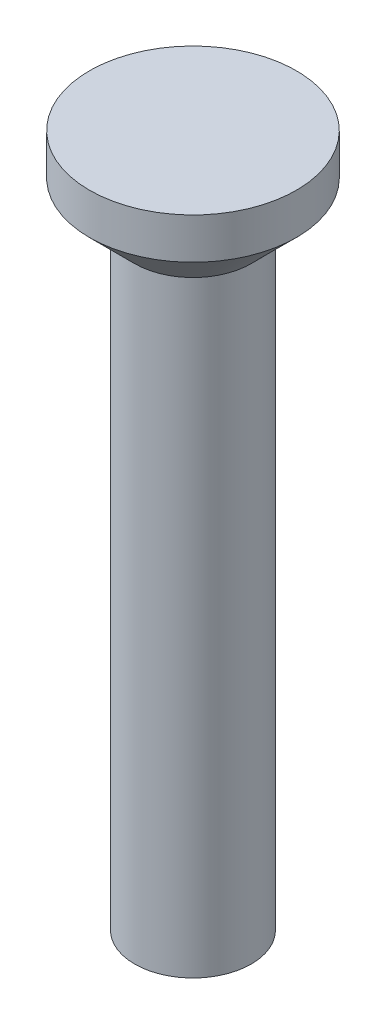
SolidWorks part; units mm, degrees
ref_plane "Спереди" through (0, 0, 0) normal (0, 0, 1) x (1, 0, 0)
ref_plane "Сверху" through (0, 0, 0) normal (0, 1, 0) x (1, 0, 0)
ref_plane "Справа" through (0, 0, 0) normal (1, 0, 0) x (0, 0, -1)
sketch "Эскиз1" plane through (0, 0, 0) normal (0, 0, 1) x (1, 0, 0)
  line L0 (0, 0) -> (25, 0)
  line L1 (25, 0) -> (25, 260)
  line L2 (25, 260) -> (44.354, 279.354)
  line L3 (44.354, 279.354) -> (44.354, 296.9242)
  line L4 (44.354, 296.9242) -> (0, 296.9242)
  line L5 (0, 348.0804) -> (0, -11.7867) construction
  line L6 (0, 0) -> (0, 296.9242)
  point P9 (0, 0)
revolve "Повернуть1" add sketch "Эскиз1" angle 360 about L5
